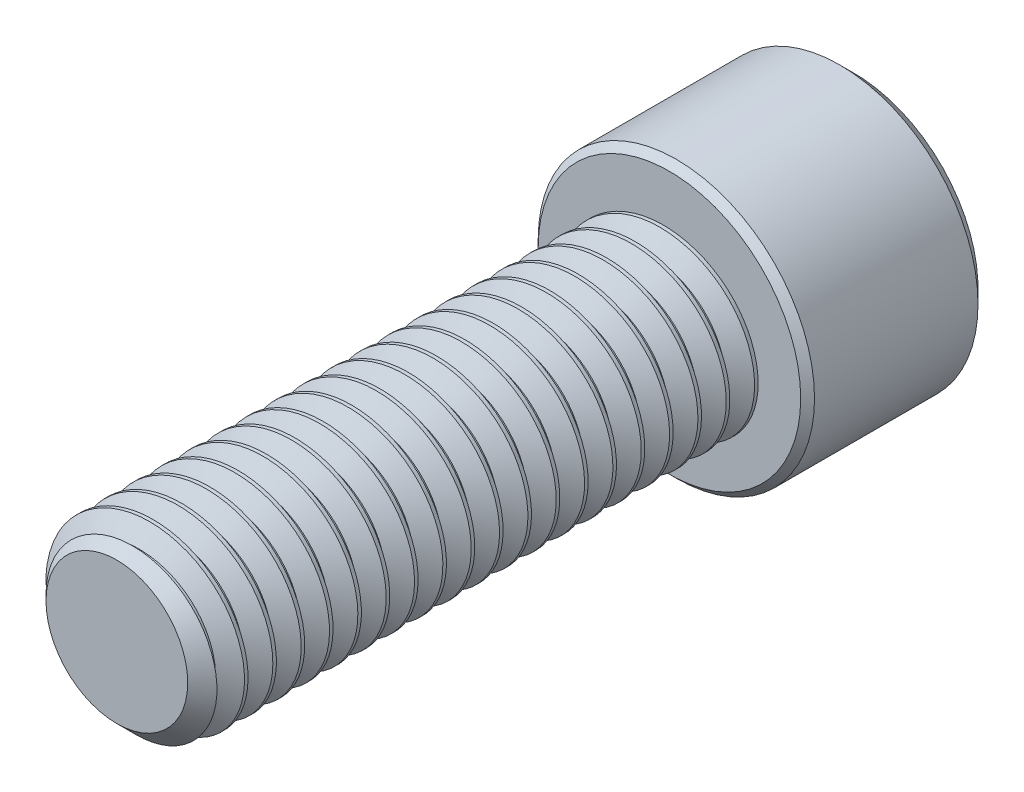
SolidWorks part; units mm, degrees
ref_plane "Front Plane" through (0, 0, 0) normal (0, 0, 1) x (1, 0, 0)
ref_plane "Top Plane" through (0, 0, 0) normal (0, 1, 0) x (1, 0, 0)
ref_plane "Right Plane" through (0, 0, 0) normal (1, 0, 0) x (0, 0, -1)
sketch "Sketch0" plane through (0, 0, 0) normal (1, 0, 0) x (0, 0, -1)
  line L0 (0, 0) -> (38.1, 0) construction
  point P2 (50.8, 0)
  point P4 (0, 0)
  dimension "D1" = 38.1
  dimension "D2" = 12.7
  dimension "Min Thread" = 0
sketch "Sketch1" plane through (0, 0, 0) normal (0, 0, 1) x (1, 0, 0)
  circle A0 centre (0, 0) radius 6.35
  dimension "OD" = 12.7
extrude "Extrude1" add sketch "Sketch1" against normal blind 38.1
sketch "Sketch2" plane through (0, 0, 0) normal (0, 0, 1) x (1, 0, 0)
  circle A0 centre (0, 0) radius 6.35 construction
  circle A1 centre (0, 0) radius 6.35
curve "Helix/Spiral1" pitch 1.9538 height 40.0538 turns 20.5 parameters "pitch"=1.9538
chamfer "Chamfer3" distance 1.4654 angle 45 1 edges at (6.35, 0, 0)
sketch "Sketch3" plane through (0, 0, 0) normal (1, 0, 0) x (0, 0, -1)
  line L0 (-1.7096, 6.35) -> (-0.9769, 5.0809)
  line L1 (-0.9769, 5.0809) -> (-0.7327, 5.0809)
  line L2 (-0.7327, 5.0809) -> (0, 6.35)
  line L3 (-1.7096, 6.35) -> (0, 6.35)
  line L4 (-0.8548, 6.35) -> (-0.8548, 5.0809) construction
  line L5 (-1.3433, 5.7155) -> (-0.3663, 5.7155) construction
  line L6 (0, 6.35) -> (0, -6.35) construction
  dimension "D1" = 0.2442
  dimension "D2" = 0.9769
  dimension "D3" = 60
sweep "Cut-Sweep1" cut profiles "Sketch3" path "Helix/Spiral1"
sketch "Sketch5" plane through (0, 0, 0) normal (1, 0, 0) x (0, 0, -1)
  line L0 (38.1, -4.5309) -> (38.1, 5.1055) construction
  line L1 (38.1, 6.35) -> (0, 6.35)
  line L2 (38.1, 6.35) -> (38.1, 0)
  line L3 (38.1, 0) -> (-2.3112, 0)
  line L4 (0, 0) -> (38.1, 0) construction
  line L5 (0, 6.35) -> (-2.3112, 0)
  line L6 (0, 0) -> (40.64, 0) construction
  dimension "D1" = 70
  dimension "D3" = 2.54
revolve "partially thread" [suppressed] add sketch "Sketch5" angle 360 about L6
sketch "Sketch6" plane through (0, 0, -38.1) normal (0, 0, -1) x (-1, 0, 0)
  circle A0 centre (0, 0) radius 9.525
  dimension "head dia" = 19.05
extrude "Extrude2" add sketch "Sketch6" along normal blind 12.7
sketch "Sketch7" plane through (0, 0, -50.8) normal (0, 0, -1) x (-1, 0, 0)
  line L1 (0, 5.4993) -> (-4.7625, 2.7496)
  line L2 (-4.7625, 2.7496) -> (-4.7625, -2.7496)
  line L3 (-4.7625, -2.7496) -> (0, -5.4993)
  line L4 (0, -5.4993) -> (4.7625, -2.7496)
  line L5 (4.7625, -2.7496) -> (4.7625, 2.7496)
  line L6 (4.7625, 2.7496) -> (0, 5.4993)
  circle A0 centre (0, 0) radius 4.7625 construction
  dimension "hex dia" = 9.525
extrude "Cut-Extrude1" cut sketch "Sketch7" against normal blind 7.1438
sketch "Sketch8" plane through (0, 0, -50.8) normal (0, 0, -1) x (-1, 0, 0)
  circle A0 centre (0, 0) radius 5.4993
extrude "Cut-Extrude2" cut sketch "Sketch8" against normal through all draft 45
chamfer "Chamfer1" distance 0.9525 angle 45 1 edges at (-9.525, 0, -50.8)
chamfer "Chamfer2" distance 0.4763 angle 45 1 edges at (-9.525, 0, -38.1)
sketch "Sketch9" plane through (0, 0, 0) normal (1, 0, 0) x (0, 0, -1)
  line L0 (0, 6.35) -> (0, -6.35) construction
  line L1 (4.8846, 6.35) -> (4.8846, -6.35) construction
  line L2 (50.8, 9.525) -> (50.8, -9.525) construction
  line L3 (38.1, 9.525) -> (38.1, -9.525) construction
  line L4 (38.1, 9.0487) -> (38.1, -9.0487) construction
  line L5 (50.8, -8.5725) -> (50.8, 8.5725) construction
  line L6 (38.1, -9.525) -> (38.1, 9.525) construction
  line L7 (0, 4.8846) -> (0, -4.8846) construction
  line L8 (-1.7096, 6.35) -> (0, 6.35) construction
  line L9 (4.8846, 0) -> (0, 0) construction
  dimension "D1" = 4.8846
equation "\"D3@Helix/Spiral1\" = \"screw length@Extrude1\"+\"pitch@Helix/Spiral1\""
equation "\"D1@Sketch3\" = \"pitch@Helix/Spiral1\"*.125"
equation "\"D2@Sketch3\" = \"pitch@Helix/Spiral1\"*.5"
equation "\"D1@Cut-Extrude1\" = \"hex dia@Sketch7\"*.75"
equation "\"D1@Chamfer1\" = \"head dia@Sketch6\"*.05"
equation "\"D1@Sketch9\" = \"pitch@Helix/Spiral1\"*2.50"
equation "\"D1@Chamfer2\" = \"D1@Chamfer1\"/2"
equation "\"D1@Chamfer3\" = \"pitch@Helix/Spiral1\"*.750"
equation "\"D1@Sketch0\" = \"screw length@Extrude1\""
equation "\"D2@Sketch0\" = \"head depth@Extrude2\""
